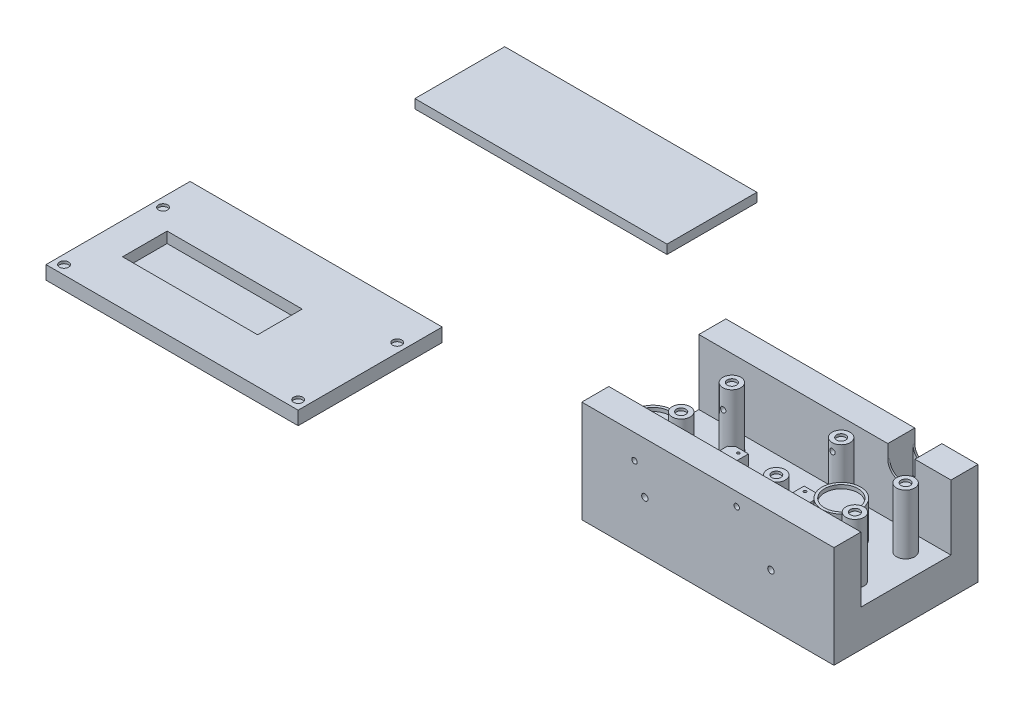
SolidWorks part; units mm, degrees
ref_plane "Front Plane" through (0, 0, 0) normal (0, 0, 1) x (1, 0, 0)
ref_plane "Top Plane" through (0, 0, 0) normal (0, 1, 0) x (1, 0, 0)
ref_plane "Right Plane" through (0, 0, 0) normal (1, 0, 0) x (0, 0, -1)
sketch "Sketch1" plane through (0, 0, 0) normal (0, 1, 0) x (1, 0, 0)
  line L1 (-125, -50) -> (125, -50)
  line L2 (-125, -50) -> (-125, 50)
  line L3 (-125, 50) -> (125, 50)
  line L4 (125, -50) -> (125, 50)
  line L5 (0, 50) -> (0, -50) construction
  line L6 (-125, 0) -> (125, 0) construction
  line L7 (-87.9863, 22.88) -> (-72.79, 22.88)
  line L8 (-91.88, 19.2734) -> (-91.88, -19.2734)
  line L9 (-87.9863, -22.88) -> (-72.79, -22.88)
  line L10 (-72.79, 22.88) -> (-72.79, -22.88)
  line L11 (-10.96, 22.88) -> (8.13, 22.88)
  line L12 (-10.96, 22.88) -> (-10.96, -22.88)
  line L13 (-10.96, -22.88) -> (8.13, -22.88)
  line L14 (8.13, 22.88) -> (8.13, -22.88)
  circle A0 centre (-96.485, 28.15) radius 10
  circle A1 centre (-96.485, -28.15) radius 10
  circle A2 centre (96.485, 28.15) radius 10
  circle A3 centre (96.485, -28.15) radius 10
  circle A4 centre (48.387, 4.8142) radius 21.5
  circle A5 centre (48.387, 4.8142) radius 18.55
  circle A6 centre (-96.485, 28.15) radius 5.17
  circle A7 centre (-96.485, -28.15) radius 5.17
  circle A8 centre (96.485, 28.15) radius 5.17
  circle A9 centre (96.485, -28.15) radius 5.17
  circle A10 centre (-96.485, 28.15) radius 10.5
  circle A11 centre (-96.485, -28.15) radius 10.5
  circle A12 centre (96.485, 28.15) radius 10.5
  circle A13 centre (96.485, -28.15) radius 10.5
  point P0 (0, 0)
  dimension "D3" = 20
  dimension "D6" = 53.46
  dimension "D8" = 43
  dimension "D9" = 37.1
  dimension "D15" = 10.34
  dimension "D16" = 21
  dimension "D17" = 10.34
  dimension "D1" = 250
  dimension "D2" = 100
  dimension "D4" = 192.97
  dimension "D5" = 56.3
  dimension "D7" = 58.31
  dimension "D10" = 19.09
  dimension "D11" = 45.76
  dimension "D12" = 33.12
  dimension "D13" = 114.04
  dimension "D14" = 19.09
extrude "Boss-Extrude1" add sketch "Sketch1" against normal blind 41 contours L1 L4 L3 L2
extrude "Boss-Extrude2" add sketch "Sketch1<4>" along normal blind 12 contours A1 L9 L10 L7 A0 L8 | L14 L11 L12 L13 region at (-82.1271, 0, 0) region at (-1.415, 0, 0)
sketch "Sketch1<4>" plane through (0, 0, 0) normal (0, 1, 0) x (1, 0, 0) same geometry as "Sketch1"
extrude "Boss-Extrude3" add sketch "Sketch1<5>" along normal blind 39 contours A4 A5 region at (27.4951, 0, -4.8142)
sketch "Sketch1<5>" plane through (0, 0, 0) normal (0, 1, 0) x (1, 0, 0) same geometry as "Sketch1"
extrude "Boss-Extrude4" add sketch "Sketch1<6>" along normal blind 34.9 contours A5
sketch "Sketch1<6>" plane through (0, 0, 0) normal (0, 1, 0) x (1, 0, 0) same geometry as "Sketch1"
extrude "Cut-Extrude1" cut sketch "Sketch1<9>" against normal blind 5 contours L8 A11 L9 A1 | A1 A7 | A7 | L7 A10 L8 A0 | A0 A6 | A6 | L9 A11 L8 A1 | L8 A10 L7 A0 region at (-86.582, 0, -25.3288) region at (-89.5989, 0, -20.7343) region at (-89.8817, 0, -21.0212) region at (-89.5989, 0, 20.7343) region at (-92.177, 0, 18.9935) region at (-89.8817, 0, 21.0212) region at (-96.485, 0, -28.15) region at (-96.485, 0, 28.15)
sketch "Sketch1<9>" plane through (0, 0, 0) normal (0, 1, 0) x (1, 0, 0) same geometry as "Sketch1"
extrude "Boss-Extrude7" add sketch "Sketch1<10>" along normal blind 66.2 contours A3 A9 | A9 | A2 A8 | A8 | A3 region at (86.7678, 0, -28.15) region at (86.7678, 0, 28.15) region at (96.485, 0, -28.15) region at (96.485, 0, 28.15)
sketch "Sketch1<10>" plane through (0, 0, 0) normal (0, 1, 0) x (1, 0, 0) same geometry as "Sketch1"
extrude "Boss-Extrude8" add sketch "Sketch1<11>" along normal blind 66.2 and the other way up to surface (5 mm away) separate body contours A1 A7 | A7 | A6 | A0 A6 region at (-89.8817, 0, -21.0212) region at (-89.8817, 0, 21.0212) region at (-96.485, 0, -28.15) region at (-96.485, 0, 28.15) other way up to face at (-96.485, -5, -17.65)
sketch "Sketch1<11>" plane through (0, 0, 0) normal (0, 1, 0) x (1, 0, 0) same geometry as "Sketch1"
extrude "Cut-Extrude2" cut sketch "Sketch1<12>" against normal blind 2.75 from surface contours A7 | A6 | A9 | A8 starting at face at (-96.485, 66.2, -18.15)
sketch "Sketch1<12>" plane through (0, 0, 0) normal (0, 1, 0) x (1, 0, 0) same geometry as "Sketch1"
sketch "Sketch3" plane through (0, 12, 0) normal (0, 1, 0) x (1, 0, 0)
  circle A0 centre (-79.2548, 18.1338) radius 1.5
  circle A1 centre (-79.2548, 0.1338) radius 1.5
  circle A2 centre (-5.2548, 18.1338) radius 1.5
  circle A3 centre (-5.2548, 0.1338) radius 1.5
  dimension "D1" = 3
  dimension "D2" = 18
  dimension "D3" = 74
  dimension "D4" = 8.02
  dimension "D5" = 19.93
extrude "Cut-Extrude3" cut sketch "Sketch3" against normal blind 12
sketch "Sketch4" plane through (0, -41, 0) normal (0, -1, 0) x (1, 0, 0)
  line L1 (-120, 30) -> (-39.4754, 30)
  line L2 (-120, 30) -> (-120, -19.5)
  line L3 (-120, -19.5) -> (30, -19.5)
  line L4 (30, 30) -> (30, -19.5)
  line L5 (-125, 50) -> (-125, -50) construction
  line L6 (-125, 50) -> (125, 50) construction
  line L7 (-15.8404, 30) -> (30, 30)
  arc A0 (-15.8404, 30) -> (-39.4754, 30) centre (-27.6579, 30) ccw
  point P9 (-27.6579, 30)
  point P10 (17.5557, 32.0804)
  point P11 (18.0739, 30)
  dimension "D1" = 150
  dimension "D2" = 49.5
  dimension "D3" = 20
  dimension "D4" = 5
extrude "Cut-Extrude4" cut sketch "Sketch4" against normal blind 31 contours L1 A0 L7 L4 L3 L2
sketch "Sketch5" plane through (-125, 0, 0) normal (-1, 0, 0) x (0, 0, 1)
  line L0 (-50, 0) -> (-50, -41)
  line L1 (-50, -41) -> (50, -41)
  line L2 (50, -41) -> (50, 0)
  line L3 (50, 0) -> (-50, 0)
extrude "Boss-Extrude9" add sketch "Sketch5" along normal blind 30
sketch "Sketch6" plane through (0, 0, 0) normal (0, 1, 0) x (1, 0, 0)
  line L0 (-130.5, -25.5) -> (-130.5, -47) construction
  line L1 (-155, -50) -> (125, -50) construction
  line L2 (-130.5, -25.5) -> (-155, -25.5) construction
  line L3 (-155, -50) -> (-155, 50) construction
  line L4 (-130.5, -25.5) -> (-152, -25.5) construction
  circle A0 centre (-130.5, -25.5) radius 21.5
  circle A1 centre (-130.5, -25.5) radius 18.55
  dimension "D1" = 43
  dimension "D2" = 37.1
  dimension "D3" = 3
  dimension "D4" = 3
extrude "Boss-Extrude10" add sketch "Sketch6" along normal blind 39
sketch "Sketch7" plane through (0, 0, 0) normal (0, 1, 0) x (1, 0, 0)
  circle A0 centre (-130.5, -25.5) radius 18.55
extrude "Boss-Extrude11" add sketch "Sketch7" along normal blind 35
sketch "Sketch8" plane through (-155, 0, 0) normal (-1, 0, 0) x (0, 0, 1)
  line L0 (4, 30.377) -> (4, -41) construction
  line L1 (4, 39) -> (4, 0) construction
  line L2 (-50, -41) -> (50, -41) construction
  line L3 (50, -41) -> (50, 0) construction
  line L4 (47, 20.3949) -> (47, -41) construction
  line L5 (47, 0) -> (47, 39) construction
  dimension "D1" = 46
  dimension "D2" = 3
sketch "Sketch10" plane through (0, 0, 0) normal (0, 1, 0) x (1, 0, 0)
  line L0 (-155, 0) -> (125, 0) construction
  line L1 (-155, -50) -> (-155, 50) construction
  line L2 (125, -50) -> (125, 50) construction
  line L3 (17, -36) -> (17, -46) construction
  line L4 (-155, -50) -> (125, -50) construction
  circle A0 centre (17, -36) radius 10
  circle A1 centre (17, 36) radius 10
  circle A2 centre (17, -36) radius 5.09
  circle A3 centre (17, 36) radius 5.09
  dimension "D1" = 20
  dimension "D4" = 10.18
  dimension "D2" = 4
  dimension "D3" = 108
extrude "Boss-Extrude12" add sketch "Sketch10" along normal blind 66.2
sketch "Sketch11" plane through (0, 0, 0) normal (0, 1, 0) x (1, 0, 0)
  circle A0 centre (17, -36) radius 5.17
  circle A1 centre (17, 36) radius 5.17
  dimension "D1" = 10.34
  dimension "D2" = 10.34
extrude "Boss-Extrude13" add sketch "Sketch11" along normal blind 63.45
sketch "Sketch9" plane through (0, 0, 50) normal (0, 0, 1) x (1, 0, 0)
  line L0 (-96.485, 66.2) -> (-96.485, 0) construction
  line L1 (-86.485, 66.2) -> (-106.485, 66.2) construction
  line L2 (-155, 0) -> (125, 0) construction
  line L3 (-96.485, 0) -> (-96.485, 45) construction
  line L4 (-96.485, 0) -> (-96.485, 57.6) construction
  line L5 (17, 66.2) -> (17, 0) construction
  line L6 (22.09, 66.2) -> (11.91, 66.2) construction
  line L7 (17, 0) -> (17, 57.6) construction
  circle A0 centre (-96.485, 45) radius 3
  circle A1 centre (17, 57.6) radius 3
  dimension "D2" = 6
  dimension "D5" = 6
  dimension "D1" = 45
  dimension "D3" = 57.6
  dimension "D4" = 57.6
extrude "Cut-Extrude5" cut sketch "Sketch9" against normal through all both and the other way through all
sketch "Sketch15" plane through (0, 0, 50) normal (0, 0, 1) x (1, 0, 0)
  line L0 (-155, 15.6) -> (125, 15.6) construction
  line L1 (-155, -41) -> (125, -41)
  line L2 (-155, -41) -> (-155, 72.2)
  line L3 (-155, 72.2) -> (125, 72.2)
  line L4 (125, -41) -> (125, 72.2)
  line L6 (-155, 15.6) -> (-85, 15.6) construction
  line L7 (-85, 15.6) -> (55, 15.6) construction
  circle A0 centre (-85, 15.6) radius 3.5
  circle A1 centre (55, 15.6) radius 3.5
  dimension "D5" = 7
  dimension "D6" = 7
  dimension "D1" = 113.2
  dimension "D2" = 280
  dimension "D3" = 70
  dimension "D4" = 140
extrude "Boss-Extrude17" add sketch "Sketch15" along normal blind 30
sketch "Sketch20" plane through (0, 0, 0) normal (0, 1, 0) x (1, 0, 0)
  line L0 (-605.7799, 235.3036) -> (-325.7799, 235.3036) construction
  line L1 (-605.7799, 285.3036) -> (-325.7799, 285.3036)
  line L2 (-605.7799, 285.3036) -> (-605.7799, 185.3036)
  line L3 (-605.7799, 185.3036) -> (-325.7799, 185.3036)
  line L4 (-325.7799, 285.3036) -> (-325.7799, 185.3036)
  circle A0 centre (-547.2649, 263.4536) radius 5.05
  circle A1 centre (-547.2649, 263.4536) radius 10.05
  circle A2 centre (-433.7799, 271.3036) radius 5.05
  circle A3 centre (-433.7799, 271.3036) radius 10.05
  circle A4 centre (-354.2949, 263.4536) radius 5.05
  circle A5 centre (-354.2949, 263.4536) radius 10.05
  circle A6 centre (-547.2649, 207.1536) radius 5.05
  circle A7 centre (-547.2649, 207.1536) radius 10.05
  circle A8 centre (-433.7799, 199.3036) radius 5.05
  circle A9 centre (-433.7799, 199.3036) radius 10.05
  circle A10 centre (-354.2949, 207.1536) radius 5.05
  circle A11 centre (-354.2949, 207.1536) radius 10.05
  circle A12 centre (-581.2799, 209.8036) radius 18.55
  circle A13 centre (-402.3929, 240.1179) radius 18.55
  dimension "D1" = 10.1
  dimension "D2" = 20.1
  dimension "D3" = 10.1
  dimension "D4" = 20.1
  dimension "D5" = 10.1
  dimension "D6" = 20.1
  dimension "D7" = 37.1
  dimension "D8" = 37.1
extrude "Boss-Extrude18" add sketch "Sketch20" against normal blind 4 separate body contours L2 L0 A13 L4 L1 A1 A3 A5 | L0 L2 L3 L4 A13 A12 A7 A9 A11 region at (-471.0616, 0, -260.7215) region at (-458.7027, 0, -210.2185)
sketch "Sketch21" plane through (0, 0, 0) normal (0, 1, 0) x (1, 0, 0)
  line L0 (-605.7799, 235.3036) -> (-325.7799, 235.3036) construction
  line L1 (-605.7799, 285.3036) -> (-605.7799, 185.3036) construction
  line L2 (-325.7799, 285.3036) -> (-325.7799, 185.3036) construction
  line L4 (-605.7799, 285.3036) -> (-325.7799, 285.3036)
  line L5 (-605.7799, 285.3036) -> (-605.7799, 185.3036)
  line L6 (-605.7799, 185.3036) -> (-325.7799, 185.3036)
  line L7 (-325.7799, 285.3036) -> (-325.7799, 185.3036)
  circle A0 centre (-547.2649, 263.4536) radius 5.17
  circle A1 centre (-433.7799, 271.3036) radius 5.17
  circle A2 centre (-354.2949, 263.4536) radius 5.17
  circle A3 centre (-354.2949, 207.1536) radius 5.17
  circle A4 centre (-433.7799, 199.3036) radius 5.17
  circle A5 centre (-547.2649, 207.1536) radius 5.17
  dimension "D1" = 10.34
  dimension "D2" = 10.34
  dimension "D3" = 10.34
  dimension "D4" = 10.34
  dimension "D5" = 10.34
  dimension "D6" = 10.34
extrude "Boss-Extrude19" add sketch "Sketch21" along normal blind 2.75
sketch "Sketch22" plane through (0, 2.75, 0) normal (0, 1, 0) x (1, 0, 0)
  line L1 (-605.7799, 285.3036) -> (-325.7799, 285.3036)
  line L2 (-605.7799, 285.3036) -> (-605.7799, 185.3036)
  line L3 (-605.7799, 185.3036) -> (-325.7799, 185.3036)
  line L4 (-325.7799, 285.3036) -> (-325.7799, 185.3036)
extrude "Boss-Extrude20" add sketch "Sketch22" along normal blind 3.25
sketch "Sketch23" plane through (0, -41, 0) normal (0, -1, 0) x (1, 0, 0)
  circle A0 centre (-27.6579, 30) radius 11.8175
  point P3 (0, 0)
sketch "Sketch24" plane through (0, -41, 0) normal (0, -1, 0) x (1, 0, 0)
  circle A0 centre (-27.6579, 30) radius 11.8175
extrude "Cut-Extrude9" cut sketch "Sketch24" against normal through all both and the other way through all
sketch "Sketch25" plane through (0, -41, 0) normal (0, -1, 0) x (1, 0, 0)
  line L0 (-155, 80) -> (-155, -50) construction
  line L1 (-155, 80) -> (125, 80)
  line L2 (-155, 80) -> (-155, -50)
  line L3 (-155, -50) -> (125, -50)
  line L4 (125, 80) -> (125, -50)
  line L5 (-120, 30) -> (30, 30)
  line L6 (-120, 30) -> (-120, -19.5)
  line L7 (-120, -19.5) -> (30, -19.5)
  line L8 (30, 30) -> (30, -19.5)
  line L9 (-15, -50) -> (-15, 80) construction
  line L10 (-155, 15) -> (125, 15) construction
  circle A0 centre (-145, 70) radius 5.17
  circle A1 centre (-145, -40) radius 5.17
  circle A2 centre (115, -40) radius 5.17
  circle A3 centre (115, 70) radius 5.17
  dimension "D1" = 10.34
  dimension "D2" = 10
  dimension "D4" = 10.34
  dimension "D5" = 10.34
  dimension "D6" = 10.34
  dimension "D3" = 10
extrude "Cut-Extrude10" cut sketch "Sketch25" against normal blind 2.75 and the other way through all contours A1 | A3 | A2 | A0 region at (-145, -41, 70) region at (-145, -41, -40) region at (115, -41, -40) region at (115, -41, 70)
sketch "Sketch27" plane through (0, -41, 0) normal (0, -1, 0) x (1, 0, 0)
  line L0 (-697.9163, 132.1026) -> (-697.9163, 2.1026) construction
  line L1 (-697.9163, 132.1026) -> (-417.9163, 132.1026)
  line L2 (-697.9163, 132.1026) -> (-697.9163, 2.1026)
  line L3 (-697.9163, 2.1026) -> (-417.9163, 2.1026)
  line L4 (-417.9163, 132.1026) -> (-417.9163, 2.1026)
  line L5 (-662.9163, 82.1026) -> (-512.9163, 82.1026)
  line L6 (-662.9163, 82.1026) -> (-662.9163, 32.6026)
  line L7 (-662.9163, 32.6026) -> (-512.9163, 32.6026)
  line L8 (-512.9163, 82.1026) -> (-512.9163, 32.6026)
  line L9 (-557.9163, 2.1026) -> (-557.9163, 132.1026) construction
  line L10 (-697.9163, 67.1026) -> (-417.9163, 67.1026) construction
  circle A0 centre (-687.9163, 122.1026) radius 5.05
  circle A1 centre (-687.9163, 12.1026) radius 5.05
  circle A2 centre (-427.9163, 12.1026) radius 5.05
  circle A3 centre (-427.9163, 122.1026) radius 5.05
  dimension "D1" = 10.1
  dimension "D2" = 10
  dimension "D3" = 10
extrude "Boss-Extrude21" add sketch "Sketch27" along normal blind 2.75 separate body
sketch "Sketch28" plane through (0, -43.75, 0) normal (0, -1, 0) x (1, 0, 0)
  line L1 (-697.9163, 132.1026) -> (-417.9163, 132.1026)
  line L2 (-697.9163, 132.1026) -> (-697.9163, 2.1026)
  line L3 (-697.9163, 2.1026) -> (-417.9163, 2.1026)
  line L4 (-417.9163, 132.1026) -> (-417.9163, 2.1026)
  line L5 (-662.9163, 82.1026) -> (-512.9163, 82.1026)
  line L6 (-662.9163, 82.1026) -> (-662.9163, 32.6026)
  line L7 (-662.9163, 32.6026) -> (-512.9163, 32.6026)
  line L8 (-512.9163, 82.1026) -> (-512.9163, 32.6026)
extrude "Boss-Extrude22" add sketch "Sketch28" along normal blind 9.25
sketch "Sketch29" plane through (0, -53, 0) normal (0, -1, 0) x (1, 0, 0)
  line L1 (-697.9163, 132.1026) -> (-417.9163, 132.1026)
  line L2 (-697.9163, 132.1026) -> (-697.9163, 2.1026)
  line L3 (-697.9163, 2.1026) -> (-417.9163, 2.1026)
  line L4 (-417.9163, 132.1026) -> (-417.9163, 2.1026)
extrude "Boss-Extrude23" add sketch "Sketch29" along normal blind 3
sketch "Sketch31" plane through (0, 0, -50) normal (0, 0, -1) x (-1, 0, 0)
  line L0 (-69.887, 39) -> (-69.887, 0) construction
  line L1 (-125, 72.2) -> (-84.937, 72.2)
  line L2 (-125, 72.2) -> (-125, -41)
  line L3 (-125, -41) -> (155, -41)
  line L4 (155, 72.2) -> (155, -41)
  line L5 (-84.937, 57.15) -> (-84.937, 72.2) construction
  line L6 (-69.887, 39) -> (-69.887, 72.2) construction
  line L7 (-69.887, 72.2) -> (-69.887, 57.15) construction
  line L8 (-54.837, 57.15) -> (-54.837, 72.2) construction
  line L9 (-84.937, 57.15) -> (-84.937, 72.2)
  line L10 (-54.837, 57.15) -> (-54.837, 72.2)
  line L11 (-54.837, 72.2) -> (155, 72.2)
  arc A0 (-84.937, 57.15) -> (-54.837, 57.15) centre (-69.887, 57.15) ccw
  dimension "D1" = 15.05
  dimension "D2" = 30.1
sketch "Sketch33" plane through (0, 0, 80) normal (0, 0, 1) x (1, 0, 0)
  circle A0 centre (-96.485, 45) radius 3
  circle A1 centre (17, 57.6) radius 3
  dimension "D1" = 6
  dimension "D2" = 6
extrude "Cut-Extrude11" cut sketch "Sketch33" against normal blind 130
sketch "Sketch34" plane through (-155, 0, 0) normal (-1, 0, 0) x (0, 0, 1)
  line L1 (4, -41) -> (4, -25.5) construction
  line L2 (4, 30.377) -> (4, -41) construction
  circle A0 centre (4, -25.5) radius 3
  dimension "D2" = 6
  dimension "D1" = 15.5
extrude "Cut-Extrude12" cut sketch "Sketch34" against normal blind 40
extrude "Boss-Extrude24" add sketch "Sketch31" along normal blind 30
sketch "Sketch35" plane through (0, 72.2, 0) normal (0, 1, 0) x (1, 0, 0)
  line L0 (69.887, 50) -> (69.887, 80) construction
  line L1 (54.837, 50) -> (84.937, 50) construction
  line L2 (84.937, 80) -> (54.837, 80) construction
  line L3 (69.887, 50) -> (69.887, 52) construction
  line L4 (69.887, 52) -> (54.837, 52)
  line L5 (54.837, 80) -> (54.837, 50) construction
  line L6 (54.837, 52) -> (54.837, 78)
  line L8 (84.937, 80) -> (84.937, 50) construction
  line L9 (84.937, 80) -> (84.937, 52)
  line L10 (84.937, 80) -> (84.937, 50) construction
  line L11 (84.937, 52) -> (69.887, 52)
  line L12 (54.837, 78) -> (84.937, 78)
  line L13 (84.937, 78) -> (84.937, 52)
  dimension "D1" = 2
  dimension "D2" = 26
extrude "Cut-Extrude13" cut sketch "Sketch35" against normal blind 45 contours L12 L6 L4 L11 L9 region at (69.887, 72.2, -65)
sketch "Sketch36" plane through (0, 0, 2.1026) normal (0, 0, -1) x (-1, 0, 0)
  line L1 (417.9163, -41) -> (697.9163, -41)
  line L2 (417.9163, -41) -> (417.9163, -56)
  line L3 (417.9163, -56) -> (697.9163, -56)
  line L4 (697.9163, -41) -> (697.9163, -56)
extrude "Boss-Extrude25" add sketch "Sketch36" along normal blind 30
sketch "Sketch37" plane through (0, 0, -185.3036) normal (0, 0, 1) x (1, 0, 0)
  line L1 (-605.7799, 6) -> (-325.7799, 6)
  line L2 (-605.7799, 6) -> (-605.7799, -4)
  line L3 (-605.7799, -4) -> (-325.7799, -4)
  line L4 (-325.7799, 6) -> (-325.7799, -4)
extrude "Cut-Extrude14" cut sketch "Sketch37" against normal blind 0.1
sketch "Sketch38" plane through (0, 0, -285.3036) normal (0, 0, -1) x (-1, 0, 0)
  line L1 (325.7799, 6) -> (605.7799, 6)
  line L2 (325.7799, 6) -> (325.7799, -4)
  line L3 (325.7799, -4) -> (605.7799, -4)
  line L4 (605.7799, 6) -> (605.7799, -4)
extrude "Cut-Extrude15" cut sketch "Sketch38" against normal blind 0.1
sketch "Sketch39" plane through (0, 72.2, 0) normal (0, 1, 0) x (1, 0, 0)
  line L0 (-96.485, 38.65) -> (-96.485, -38.65) construction
  circle A0 centre (-96.485, 28.15) radius 10.5 construction
  arc A1 (-87.4033, 22.88) -> (-91.88, 18.7137) centre (-96.485, 28.15) ccw construction
  circle A2 centre (-96.485, -28.15) radius 10.5 construction
